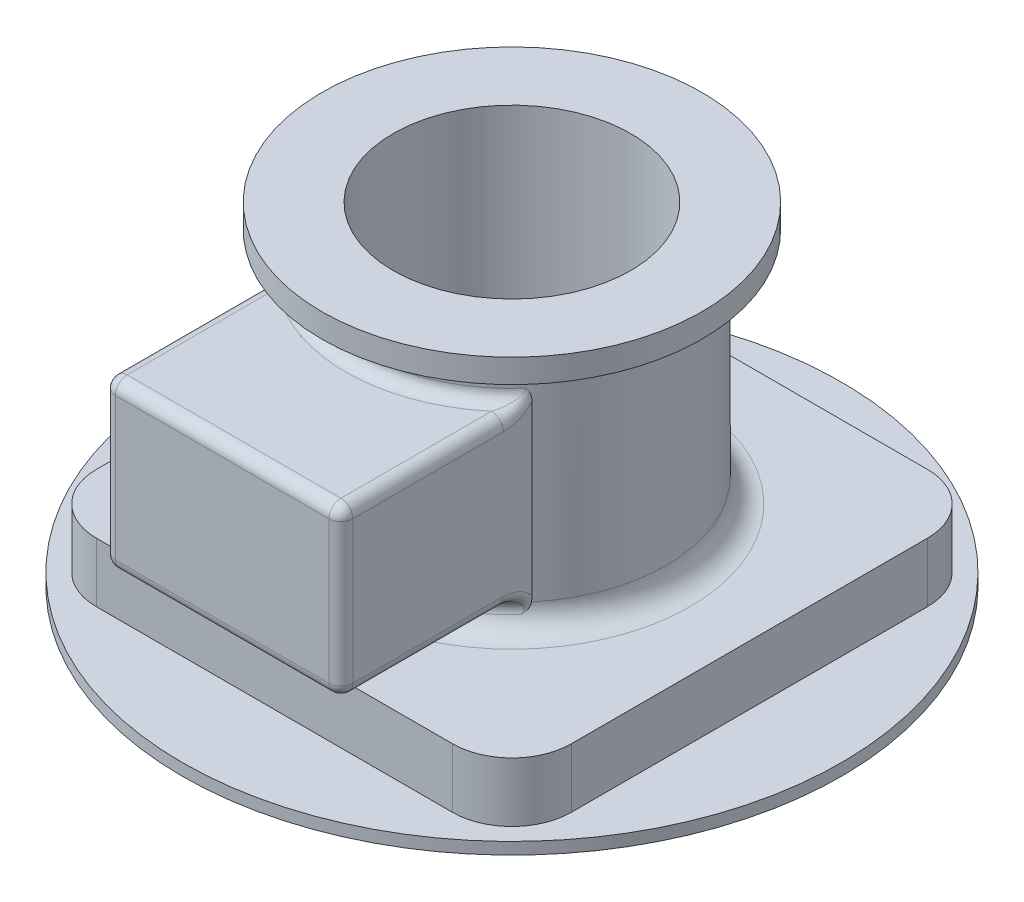
SolidWorks part; units mm, degrees
ref_plane "Front Plane" through (0, 0, 0) normal (0, 0, 1) x (1, 0, 0)
ref_plane "Top Plane" through (0, 0, 0) normal (0, 1, 0) x (1, 0, 0)
ref_plane "Right Plane" through (0, 0, 0) normal (1, 0, 0) x (0, 0, -1)
sketch "Sketch1" plane through (0, 0, 0) normal (0, 1, 0) x (1, 0, 0)
  circle A0 centre (0, 0) radius 277.5
  dimension "D1" = 555
extrude "Boss-Extrude1" add sketch "Sketch1" against normal blind 10
sketch "Sketch2" plane through (0, 0, 0) normal (0, 1, 0) x (1, 0, 0)
  line L1 (-200, -200) -> (200, -200)
  line L2 (-200, -200) -> (-200, 200)
  line L3 (-200, 200) -> (200, 200)
  line L4 (200, -200) -> (200, 200)
  line L5 (-200, -200) -> (200, 200) construction
  line L6 (-200, 200) -> (200, -200) construction
  point P0 (0, 0)
  dimension "D1" = 400
  dimension "D2" = 400
extrude "Boss-Extrude2" add sketch "Sketch2" along normal blind 50
fillet "Fillet2" radius 50 1 edges at (-200, 25, -200)
fillet "Fillet3" radius 50 3 edges at (200, 25, 200) (200, 25, -200) (-200, 25, 200)
sketch "Sketch4" plane through (0, 50, 0) normal (0, 1, 0) x (1, 0, 0)
  circle A0 centre (0, 0) radius 130
  dimension "D1" = 260
extrude "Boss-Extrude3" add sketch "Sketch4" along normal blind 200
sketch "Sketch5" plane through (0, 250, 0) normal (0, 1, 0) x (1, 0, 0)
  circle A0 centre (0, 0) radius 160
  dimension "D1" = 320
extrude "Boss-Extrude4" add sketch "Sketch5" along normal blind 20
sketch "Sketch6" plane through (0, 0, 0) normal (0, 0, 1) x (1, 0, 0)
  line L0 (0, 384.54) -> (0, -115.3139) construction
  line L2 (-100, 76.0476) -> (100, 76.0476)
  line L3 (-100, 76.0476) -> (-100, 216.0476)
  line L4 (-100, 216.0476) -> (100, 216.0476)
  line L5 (100, 76.0476) -> (100, 216.0476)
  line L6 (-100, 76.0476) -> (100, 216.0476) construction
  line L7 (-100, 216.0476) -> (100, 76.0476) construction
  point P3 (0, 146.0476)
  dimension "D1" = 200
  dimension "D2" = 140
extrude "Boss-Extrude5" add sketch "Sketch6" along normal blind 244
fillet "Fillet4" radius 20 1 edges at (0, 50, 130)
sketch "Sketch8" plane through (0, 270, 0) normal (0, 1, 0) x (1, 0, 0)
  circle A0 centre (0, 0) radius 100
  dimension "D1" = 200
extrude "Cut-Extrude2" cut sketch "Sketch8" against normal blind 171 contours A0
fillet "Fillet6" radius 10 6 edges at (0, 76.0476, 130) (0, 216.0476, 130) (-100, 146.0476, 244) (-100, 76.0476, 163.5331) (-100, 146.0476, 83.0662) (-100, 216.0476, 163.5331)
fillet "Fillet7" radius 10 5 edges at (-97.0711, 78.9765, 241.0711) (-97.0711, 213.1187, 241.0711) (100, 146.0476, 244) (5, 76.0476, 244) (5, 216.0476, 244)
fillet "Fillet11" radius 10 3 edges at (97.0711, 213.1187, 241.0711) (100, 221.3964, 84.8509) (100, 216.0476, 165.9898)
fillet "Fillet12" radius 10 3 edges at (97.0711, 78.9765, 241.0711) (100, 70.2325, 85.7515) (100, 76.0476, 166.5698)
